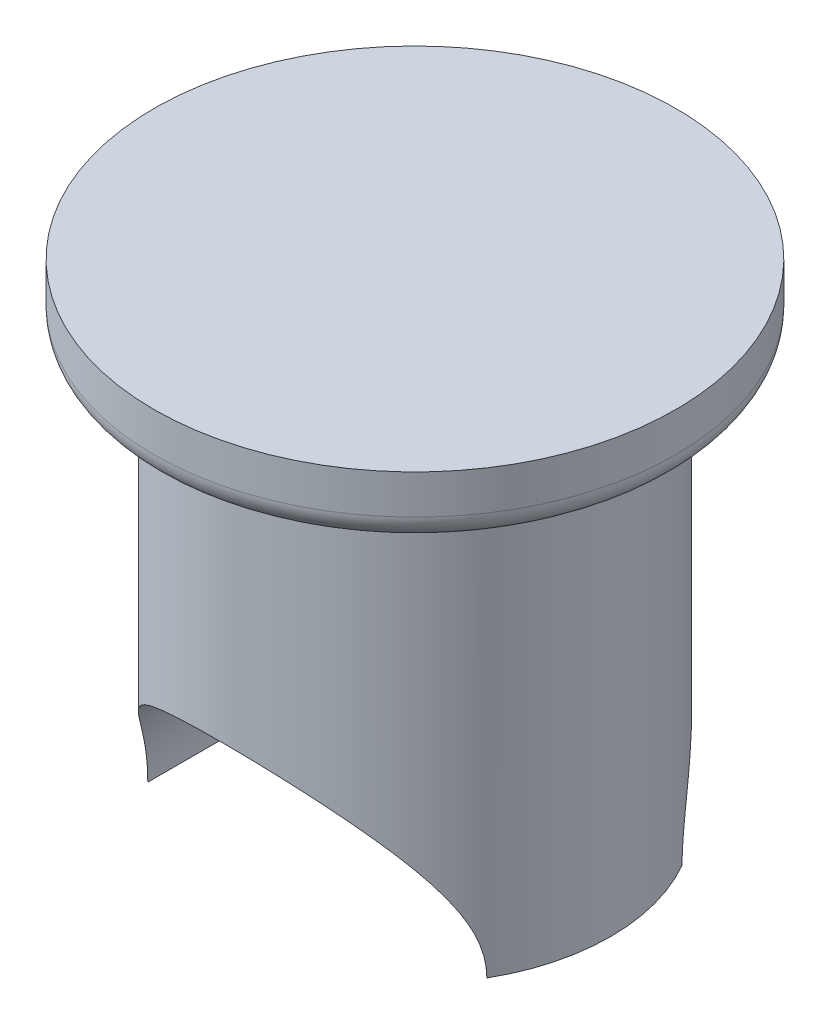
SolidWorks part; units mm, degrees
ref_plane "Front Plane" through (0, 0, 0) normal (0, 0, 1) x (1, 0, 0)
ref_plane "Top Plane" through (0, 0, 0) normal (0, 1, 0) x (1, 0, 0)
ref_plane "Right Plane" through (0, 0, 0) normal (1, 0, 0) x (0, 0, -1)
sketch "Sketch2" plane through (0, 0, 0) normal (0, 1, 0) x (1, 0, 0)
  circle A0 centre (0, 0) radius 15
  dimension "D1" = 30
extrude "Boss-Extrude1" add sketch "Sketch2" along normal blind 32.5
sketch "Sketch3" plane through (0, 0, 0) normal (0, 0, 1) x (1, 0, 0)
  circle A0 centre (0, 0) radius 13
  dimension "D1" = 26
extrude "Cut-Extrude1" cut sketch "Sketch3" against normal blind 50 and the other way blind 50
sketch "Sketch5" plane through (0, 32.5, 0) normal (0, 1, 0) x (1, 0, 0)
  circle A0 centre (0, 0) radius 20
extrude "Boss-Extrude2" add sketch "Sketch5" along normal blind 5
fillet "Fillet1" radius 2 2 edges at (0, 32.5, 20) (0, 32.5, 15)
